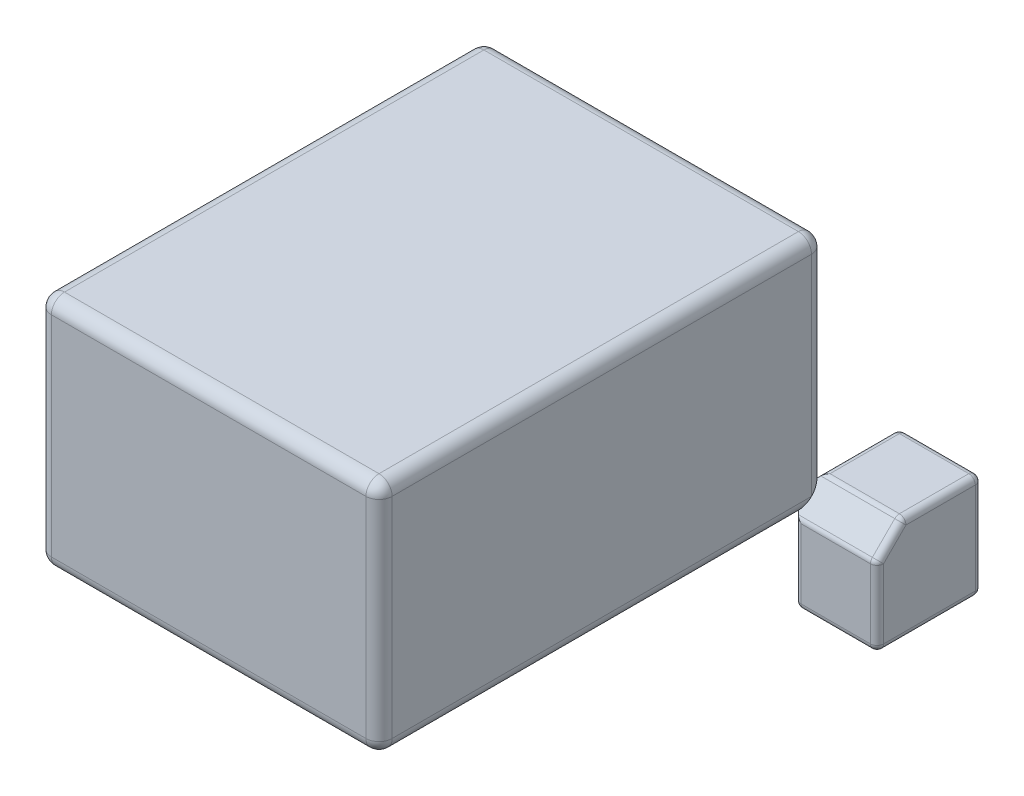
SolidWorks part; units mm, degrees
ref_plane "Front Plane" through (0, 0, 0) normal (0, 0, 1) x (1, 0, 0)
ref_plane "Top Plane" through (0, 0, 0) normal (0, 1, 0) x (1, 0, 0)
ref_plane "Right Plane" through (0, 0, 0) normal (1, 0, 0) x (0, 0, -1)
sketch "Sketch1" plane through (0, 0, 0) normal (0, 0, 1) x (1, 0, 0)
  line L1 (0, 0) -> (26, 0)
  line L2 (0, 0) -> (0, 18)
  line L3 (0, 18) -> (26, 18)
  line L4 (26, 0) -> (26, 18)
  dimension "D1" = 26
  dimension "D2" = 18
extrude "Boss-Extrude1" add sketch "Sketch1" along normal blind 34
sketch "Sketch2" plane through (0, 0, 0) normal (0, 0, -1) x (-1, 0, 0)
  line L0 (-26, 0) -> (-26, 18) construction
  line L1 (-24, 2) -> (-32, 2)
  line L2 (-24, 2) -> (-24, -6)
  line L3 (-24, -6) -> (-32, -6)
  line L4 (-32, 2) -> (-32, -6)
  line L5 (0, 0) -> (-26, 0) construction
  dimension "D1" = 2
  dimension "D2" = 2
  dimension "D3" = 8
  dimension "D4" = 8
shell "Shell1" thickness 1
extrude "Boss-Extrude3" add sketch "Sketch2" along normal blind 6 and the other way blind 2 contours L3 L4 L1 L2
chamfer "Chamfer2" distance 2 angle 45 3 edges at (29, 2, 2) (24, 2, -3) (24, -3, 2)
fillet "Fillet1" radius 1 12 edges at (0, 9, 0) (12, 0, 0) (26, 10, 0) (13, 18, 0) (13, 0, 34) (26, 9, 34) (13, 18, 34) (0, 18, 17) (26, 18, 17) (26, 0, 18) (0, 0, 17) (0, 9, 34)
fillet "Fillet2" radius 0.5 18 edges at (32, -6, -2) (28, -6, -6) (25, -6, 1) (29, -6, 2) (24, -6, -3) (24, -3, -6) (24, 0, -3) (24, -3, 0) (29, 0, 2) (25, 1, -6) (29, 2, -6) (32, 2, -3) (29, 2, 0) (26, 2, -3) (32, -3, 2) (32, -2, -6) (26, -3, 2) (32, 1, 1)
